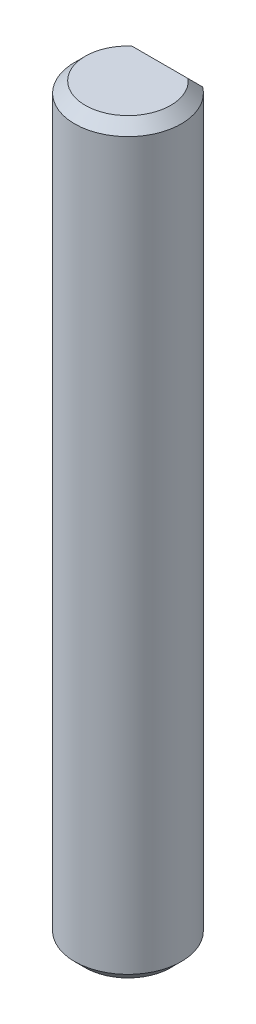
SolidWorks part; units mm, degrees
ref_plane "Front Plane" through (0, 0, 0) normal (0, 0, 1) x (1, 0, 0)
ref_plane "Top Plane" through (0, 0, 0) normal (0, 1, 0) x (1, 0, 0)
ref_plane "Right Plane" through (0, 0, 0) normal (1, 0, 0) x (0, 0, -1)
sketch "Sketch1" plane through (0, 0, 0) normal (0, 1, 0) x (1, 0, 0)
  circle A0 centre (0, 0) radius 2.5
  dimension "D1" = 5
extrude "Boss-Extrude1" add sketch "Sketch1" along normal mid plane 35
sketch "Sketch3" plane through (0, 0, 0) normal (0, 0, 1) x (1, 0, 0)
  line L0 (-11.9354, 0) -> (12.7316, 0) construction
  line L1 (-2.8942, 8) -> (2.8942, 8)
  line L2 (-2.8942, 8) -> (-2.8942, 19.4813)
  line L3 (-2.8942, 19.4813) -> (2.8942, 19.4813)
  line L4 (2.8942, 8) -> (2.8942, 19.4813)
  line L5 (-2.8942, 8) -> (2.8942, 19.4813) construction
  line L6 (-2.8942, 19.4813) -> (2.8942, 8) construction
  line L7 (-2.8942, -19.4813) -> (2.8942, -19.4813)
  line L8 (2.8942, -8) -> (2.8942, -19.4813)
  line L9 (-2.8942, -8) -> (2.8942, -8)
  line L10 (-2.8942, -8) -> (-2.8942, -19.4813)
  point P0 (0, 13.7407)
  dimension "D1" = 8
extrude "Cut-Extrude1" cut sketch "Sketch3" against normal blind 35 from offset 2 offset against normal yes
chamfer "Chamfer1" distance 0.5 angle 45 4 edges at (0, 17.5, -2) (0, 17.5, 2.5) (0, -17.5, -2) (0, -17.5, 2.5)
